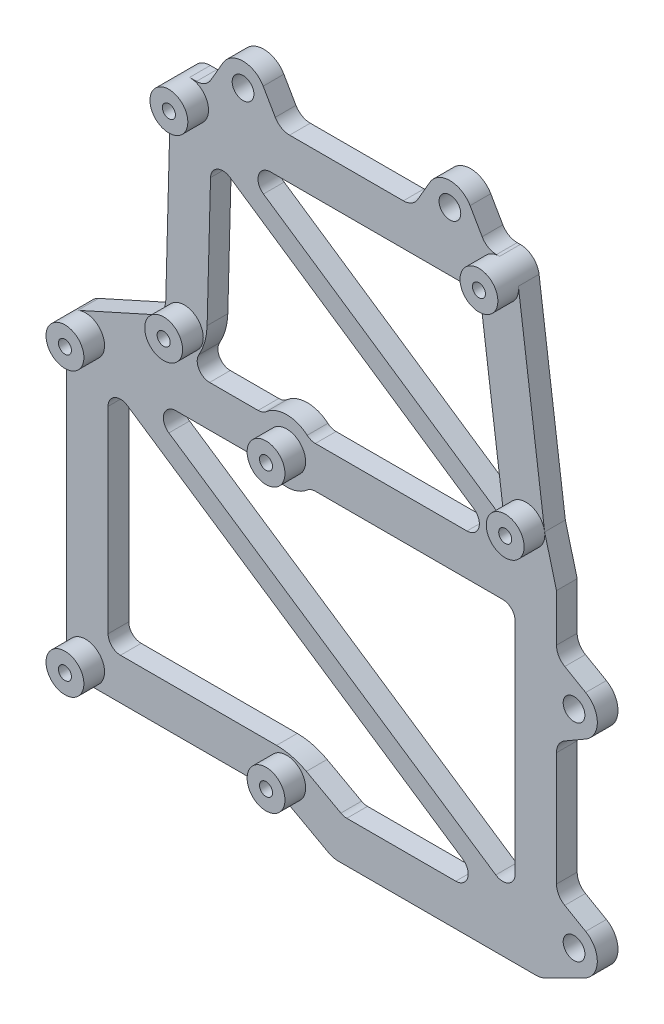
SolidWorks part; units mm, degrees
ref_plane "Front Plane" through (0, 0, 0) normal (0, 0, 1) x (1, 0, 0)
ref_plane "Top Plane" through (0, 0, 0) normal (0, 1, 0) x (1, 0, 0)
ref_plane "Right Plane" through (0, 0, 0) normal (1, 0, 0) x (0, 0, -1)
sketch "Sketch1" plane through (0, 0, 0) normal (0, 0, 1) x (1, 0, 0)
  line L0 (-89.9435, -52.835) -> (-7.3935, -52.835) construction
  line L1 (-88.6735, -4.575) -> (-13.7435, -4.575) construction
  line L2 (-89.9435, -52.835) -> (-13.7435, -4.575) construction
  line L3 (-88.6735, -4.575) -> (-7.3935, -52.835) construction
  line L4 (-88.6735, -3) -> (-13.7435, -3) construction
  line L5 (0, 0) -> (-100, 0) construction
  line L6 (0, 0) -> (0, -55.0748) construction
  line L7 (0, -55.0748) -> (-100, -55.0748) construction
  line L8 (-100, 0) -> (-100, -55.0748) construction
  line L9 (0, 0) -> (-100, -55.0748) construction
  line L10 (0, -55.0748) -> (-100, 0) construction
  line L11 (-113.8, -66.4248) -> (-65.2, -66.4248) construction
  line L12 (-62, -138.0748) -> (-117, -138.0748) construction
  line L13 (-62, -138.0748) -> (-62, -63.0748) construction
  line L14 (-62, -63.0748) -> (-117, -63.0748) construction
  line L15 (-117, -138.0748) -> (-117, -63.0748) construction
  line L16 (-62, -138.0748) -> (-117, -63.0748) construction
  line L17 (-62, -63.0748) -> (-117, -138.0748) construction
  line L18 (-65.2, -66.4248) -> (-65.2, -134.7248) construction
  line L19 (-65.2, -134.7248) -> (-113.8, -134.7248) construction
  line L20 (-65.2, -100.5748) -> (-89.5, -100.5748) construction
  line L21 (-89.5, -100.5748) -> (-89.5, -66.4248) construction
  line L22 (-94.517, -52.7145) -> (-93.2485, -4.575)
  line L23 (0, -146.0748) -> (-54, -146.0748)
  line L24 (0, -146.0748) -> (0, -63.0748)
  line L25 (0, -63.0748) -> (-54, -63.0748) construction
  line L26 (-54, -146.0748) -> (-54, -63.0748) construction
  line L27 (0, -146.0748) -> (-54, -63.0748) construction
  line L28 (0, -63.0748) -> (-54, -146.0748) construction
  line L29 (-88.6735, 0) -> (-13.7435, 0)
  line L30 (-9.2076, -3.9782) -> (-2.8576, -52.2382)
  line L31 (-2.8576, -52.2382) -> (0, -63.0748)
  line L32 (-54, -146.0748) -> (-66.3707, -139.2998)
  line L33 (-66.3707, -139.2998) -> (-113.8, -139.2998)
  line L34 (-118.375, -134.7248) -> (-118.375, -66.4248)
  line L35 (-115.6801, -62.254) -> (-94.517, -52.7145)
  circle A0 centre (-88.6735, -4.575) radius 1.575 construction
  circle A1 centre (-13.7435, -4.575) radius 1.575 construction
  circle A2 centre (-89.9435, -52.835) radius 1.575 construction
  circle A3 centre (-7.3935, -52.835) radius 1.575 construction
  circle A4 centre (-113.8, -66.4248) radius 1.575 construction
  circle A5 centre (-65.2, -66.4248) radius 1.575 construction
  circle A6 centre (-113.8, -134.7248) radius 1.575 construction
  circle A7 centre (-65.2, -134.7248) radius 1.575 construction
  circle A8 centre (-89.9435, -52.835) radius 4.575 construction
  circle A9 centre (-88.6735, -4.575) radius 4.575 construction
  circle A10 centre (-13.7435, -4.575) radius 4.575 construction
  circle A11 centre (-7.3935, -52.835) radius 4.575 construction
  circle A12 centre (-113.8, -66.4248) radius 4.575 construction
  circle A13 centre (-65.2, -66.4248) radius 4.575 construction
  circle A14 centre (-113.8, -134.7248) radius 4.575 construction
  circle A15 centre (-65.2, -134.7248) radius 4.575 construction
  arc A16 (-88.6735, 0) -> (-93.2485, -4.575) centre (-88.6735, -4.575) ccw
  arc A17 (-9.2076, -3.9782) -> (-13.7435, 0) centre (-13.7435, -4.575) ccw
  arc A18 (-118.375, -134.7248) -> (-113.8, -139.2998) centre (-113.8, -134.7248) ccw
  arc A19 (-118.375, -66.4248) -> (-115.6801, -62.254) centre (-113.8, -66.4248) cw
  point P8 (-50, -27.5374)
  point P17 (-89.5, -100.5748)
  point P31 (-27, -104.5748)
  dimension "D1" = 3.15
  dimension "D10" = 68.3
  dimension "D17" = 3
  dimension "D18" = 4.575
  dimension "D19" = 4.575
  dimension "D20" = 4.575
  dimension "D21" = 4.575
  dimension "D2" = 74.93
  dimension "D3" = 48.26
  dimension "D4" = 1.27
  dimension "D5" = 82.55
  dimension "D6" = 3
  dimension "D7" = 100
  dimension "D8" = 75
  dimension "D9" = 55
  dimension "D11" = 48.6
  dimension "D12" = 8
  dimension "D13" = 83
  dimension "D14" = 54
  dimension "D15" = 8
  dimension "D16" = 8
extrude "Boss-Extrude1" add sketch "Sketch1" along normal blind 5
fillet "Fillet1" radius 5 4 edges at (0, -146.0748, 2.5) (-54, -146.0748, 2.5) (-66.3707, -139.2998, 2.5) (-94.517, -52.7145, 2.5)
sketch "Sketch2" plane through (0, 0, 5) normal (0, 0, 1) x (1, 0, 0)
  circle A0 centre (-113.8, -66.4248) radius 1.575 construction
  circle A1 centre (-113.8, -66.4248) radius 1.575
  circle A2 centre (-7.3935, -52.835) radius 1.575 construction
  circle A3 centre (-13.7435, -4.575) radius 1.575 construction
  circle A4 centre (-13.7435, -4.575) radius 4.575 construction
  circle A5 centre (-7.3935, -52.835) radius 4.575 construction
  circle A6 centre (-89.9435, -52.835) radius 4.575 construction
  circle A7 centre (-89.9435, -52.835) radius 1.575 construction
  circle A8 centre (-88.6735, -4.575) radius 1.575 construction
  circle A9 centre (-88.6735, -4.575) radius 4.575 construction
  circle A10 centre (-65.2, -134.7248) radius 1.575 construction
  circle A11 centre (-65.2, -134.7248) radius 4.575 construction
  circle A12 centre (-65.2, -66.4248) radius 1.575 construction
  circle A13 centre (-65.2, -66.4248) radius 4.575 construction
  circle A14 centre (-113.8, -66.4248) radius 4.575 construction
  circle A15 centre (-113.8, -134.7248) radius 4.575 construction
  circle A16 centre (-113.8, -134.7248) radius 1.575 construction
  circle A17 centre (-7.3935, -52.835) radius 1.575
  circle A18 centre (-13.7435, -4.575) radius 1.575
  circle A19 centre (-13.7435, -4.575) radius 4.575
  circle A20 centre (-7.3935, -52.835) radius 4.575
  circle A21 centre (-89.9435, -52.835) radius 4.575
  circle A22 centre (-89.9435, -52.835) radius 1.575
  circle A23 centre (-88.6735, -4.575) radius 1.575
  circle A24 centre (-88.6735, -4.575) radius 4.575
  circle A25 centre (-65.2, -134.7248) radius 1.575
  circle A26 centre (-65.2, -134.7248) radius 4.575
  circle A27 centre (-65.2, -66.4248) radius 1.575
  circle A28 centre (-65.2, -66.4248) radius 4.575
  circle A29 centre (-113.8, -66.4248) radius 4.575
  circle A30 centre (-113.8, -134.7248) radius 4.575
  circle A31 centre (-113.8, -134.7248) radius 1.575
extrude "Boss-Extrude2" add sketch "Sketch2" along normal blind 5
sketch "Sketch3" plane through (0, 0, 5) normal (0, 0, 1) x (1, 0, 0)
  line L0 (-65.2, -61.4248) -> (-100.6345, -61.4248) construction
  line L1 (-65.2, -61.4248) -> (-10, -61.4248) construction
  line L2 (-93.2685, -63.1207) -> (-108.375, -69.9301) construction
  line L3 (-108.375, -69.9301) -> (-108.375, -129.2998) construction
  line L4 (-65.2, -66.4248) -> (-100.6345, -66.4248) construction
  line L5 (-10, -64.3712) -> (-12.6892, -54.1732) construction
  line L6 (-10, -136.0748) -> (-10, -64.3712) construction
  line L7 (-65.2, -66.4248) -> (-10, -66.4248) construction
  line L8 (0, -141.0748) -> (0, -63.0748) construction
  line L9 (-65.2, -71.4248) -> (-10, -71.4248) construction
  line L10 (-113.8, -66.4248) -> (-10, -136.0748) construction
  line L11 (-83.388, -10) -> (0, -66.4248) construction
  line L12 (-108.375, -73.0757) -> (-14.4868, -136.0748)
  line L13 (-101.8617, -71.4248) -> (-10, -133.0642)
  line L14 (-83.4662, -12.9657) -> (-11.8503, -61.4248)
  line L15 (-78.927, -10) -> (-12.4816, -54.9606)
  line L16 (-112.407, -64.3489) -> (-8.607, -133.9989) construction
  line L17 (-115.193, -68.5008) -> (-11.393, -138.1508) construction
  line L18 (-51.441, -136.0748) -> (-10, -136.0748) construction
  line L19 (-81.987, -7.9295) -> (1.401, -64.3543) construction
  line L20 (-18.5015, -10) -> (-83.388, -10) construction
  line L21 (-84.7891, -12.0705) -> (-1.401, -68.4954) construction
  line L22 (-83.388, -10) -> (-84.4378, -49.8409) construction
  line L30 (-10, -133.0642) -> (-10, -71.4248)
  line L31 (-12.4816, -54.9606) -> (-12.6892, -54.1732)
  line L32 (-12.6892, -54.1732) -> (-18.5015, -10)
  line L33 (-18.5015, -10) -> (-78.927, -10)
  line L34 (-83.4662, -12.9657) -> (-84.4378, -49.8409)
  line L36 (-108.375, -73.0757) -> (-108.375, -129.2998)
  line L37 (-108.375, -129.2998) -> (-67.6502, -129.2998)
  line L38 (-60.4451, -131.1436) -> (-51.441, -136.0748)
  line L39 (-51.441, -136.0748) -> (-14.4868, -136.0748)
  line L40 (0, -141.0748) -> (0, -63.0748)
  line L41 (-52.7205, -146.0748) -> (-5, -146.0748)
  line L42 (-65.2485, -139.9144) -> (-55.1222, -145.4602)
  line L43 (-113.8, -139.2998) -> (-67.6502, -139.2998)
  line L44 (-118.375, -66.4248) -> (-118.375, -134.7248)
  line L45 (-97.3779, -54.0041) -> (-115.6801, -62.254)
  line L46 (-93.2485, -4.575) -> (-94.4343, -49.5775)
  line L47 (-13.7435, 0) -> (-88.6735, 0)
  line L48 (-2.8576, -52.2382) -> (-9.2076, -3.9782)
  line L49 (0, -63.0748) -> (-2.8576, -52.2382)
  line L50 (0, -141.0748) -> (0, -63.0748)
  line L51 (-52.7205, -146.0748) -> (-5, -146.0748)
  line L52 (-65.2485, -139.9144) -> (-55.1222, -145.4602)
  line L53 (-113.8, -139.2998) -> (-67.6502, -139.2998)
  line L54 (-118.375, -66.4248) -> (-118.375, -134.7248)
  line L55 (-97.3779, -54.0041) -> (-115.6801, -62.254)
  line L56 (-93.2485, -4.575) -> (-94.4343, -49.5775)
  line L57 (-13.7435, 0) -> (-88.6735, 0)
  line L58 (-2.8576, -52.2382) -> (-9.2076, -3.9782)
  line L59 (0, -63.0748) -> (-2.8576, -52.2382)
  line L60 (-65.2, -66.4248) -> (0, -66.4248) construction
  line L61 (-65.2, -66.4248) -> (-109.225, -66.4248) construction
  line L62 (-70.8904, -71.4248) -> (-101.8617, -71.4248)
  line L63 (-59.5096, -71.4248) -> (-10, -71.4248)
  line L64 (-70.8904, -61.4248) -> (-90.4047, -61.4248)
  line L65 (-59.5096, -61.4248) -> (-11.8503, -61.4248)
  line L66 (-65.2, -71.4248) -> (-100.6345, -71.4248) construction
  arc A0 (-93.2685, -63.1207) -> (-84.4378, -49.8409) centre (-99.4326, -49.4458) ccw construction
  circle A1 centre (-113.8, -66.4248) radius 4.575 construction
  arc A2 (-118.375, -66.4248) -> (-115.6801, -62.254) centre (-113.8, -66.4248) ccw construction
  arc A3 (-70.8904, -71.4248) -> (-59.5096, -71.4248) centre (-65.2, -66.4248) ccw
  arc A27 (-18.5015, -10) -> (-18.5015, -10) centre (-18.5015, -10) ccw
  arc A28 (-83.388, -10) -> (-83.388, -10) centre (-83.388, -10) ccw
  arc A29 (-90.4047, -61.4248) -> (-84.4378, -49.8409) centre (-99.4326, -49.4458) ccw
  arc A30 (-108.375, -69.9301) -> (-108.375, -69.9301) centre (-108.375, -69.9301) ccw
  arc A31 (-108.375, -129.2998) -> (-108.375, -129.2998) centre (-108.375, -129.2998) ccw
  arc A32 (-60.4451, -131.1436) -> (-67.6502, -129.2998) centre (-67.6502, -144.2998) ccw
  arc A33 (-51.441, -136.0748) -> (-51.441, -136.0748) centre (-51.441, -136.0748) ccw
  arc A34 (-10, -136.0748) -> (-10, -136.0748) centre (-10, -136.0748) ccw
  arc A35 (-5, -146.0748) -> (0, -141.0748) centre (-5, -141.0748) ccw
  arc A36 (-55.1222, -145.4602) -> (-52.7205, -146.0748) centre (-52.7205, -141.0748) ccw
  arc A37 (-65.2485, -139.9144) -> (-67.6502, -139.2998) centre (-67.6502, -144.2998) ccw
  arc A38 (-118.375, -134.7248) -> (-113.8, -139.2998) centre (-113.8, -134.7248) ccw
  arc A39 (-115.6801, -62.254) -> (-118.375, -66.4248) centre (-113.8, -66.4248) ccw
  arc A40 (-97.3779, -54.0041) -> (-94.4343, -49.5775) centre (-99.4326, -49.4458) ccw
  arc A41 (-88.6735, 0) -> (-93.2485, -4.575) centre (-88.6735, -4.575) ccw
  arc A42 (-9.2076, -3.9782) -> (-13.7435, 0) centre (-13.7435, -4.575) ccw
  arc A43 (-5, -146.0748) -> (0, -141.0748) centre (-5, -141.0748) ccw
  arc A44 (-55.1222, -145.4602) -> (-52.7205, -146.0748) centre (-52.7205, -141.0748) ccw
  arc A45 (-65.2485, -139.9144) -> (-67.6502, -139.2998) centre (-67.6502, -144.2998) ccw
  arc A46 (-118.375, -134.7248) -> (-113.8, -139.2998) centre (-113.8, -134.7248) ccw
  arc A47 (-115.6801, -62.254) -> (-118.375, -66.4248) centre (-113.8, -66.4248) ccw
  arc A48 (-97.3779, -54.0041) -> (-94.4343, -49.5775) centre (-99.4326, -49.4458) ccw
  arc A49 (-88.6735, 0) -> (-93.2485, -4.575) centre (-88.6735, -4.575) ccw
  arc A50 (-9.2076, -3.9782) -> (-13.7435, 0) centre (-13.7435, -4.575) ccw
  arc A51 (-59.5096, -61.4248) -> (-70.8904, -61.4248) centre (-65.2, -66.4248) ccw
  circle A52 centre (-65.2, -66.4248) radius 4.575 construction
  circle A53 centre (-65.2, -66.4248) radius 4.575
  dimension "D3" = 3
  dimension "D1" = 0
  dimension "D2" = 10
  dimension "D4" = 5
  dimension "D5" = 5
  dimension "D6" = 2.5
  dimension "D7" = 2.5
  dimension "D8" = 2.5
  dimension "D9" = 2.5
extrude "Cut-Extrude1" cut sketch "Sketch3" against normal up to surface (5 mm away) contours A51 L65 L14 L34 A29 L64 | L32 L33 L15 L31 | A3 L62 L13 L30 L63 | A32 L38 L39 L12 L36 L37 region at (-76.3107, -112.748, 5) region at (-40.4429, -92.1122, 5) region at (-60.2537, -45.2476, 5) region at (-36.6741, -24.9619, 5) up to face at (-61.7558, -82.681, 0)
sketch "Sketch4" plane through (0, 0, 0) normal (0, 0, 1) x (1, 0, 0)
  line L0 (-126.2586, 4.2426) -> (4.2426, 4.2426) construction
  line L1 (4.2426, 4.2426) -> (4.2426, -135.7574) construction
  line L2 (0, 0) -> (4.2426, 4.2426) construction
  line L3 (-75.7574, 4.2426) -> (-75.7574, 0) construction
  line L4 (-80.6288, 7.0551) -> (-84.702, 0)
  line L5 (-70.886, 7.0551) -> (-66.8127, 0)
  line L6 (-84.702, 0) -> (-66.8127, 0)
  line L7 (-25.7574, 4.2426) -> (-25.7574, 0) construction
  line L8 (-30.6288, 7.0551) -> (-34.702, 0)
  line L9 (-20.886, 7.0551) -> (-16.8127, 0)
  line L10 (-34.702, 0) -> (-16.8127, 0)
  line L11 (4.2426, -85.7574) -> (0, -85.7574) construction
  line L12 (7.0551, -80.886) -> (0, -76.8127)
  line L13 (0, -141.0748) -> (0, -63.0748)
  line L14 (-52.7205, -146.0748) -> (-5, -146.0748)
  line L15 (-65.2485, -139.9144) -> (-55.1222, -145.4602)
  line L16 (-113.8, -139.2998) -> (-67.6502, -139.2998)
  line L17 (-118.375, -66.4248) -> (-118.375, -134.7248)
  line L18 (-97.3779, -54.0041) -> (-115.6801, -62.254)
  line L19 (-93.2485, -4.575) -> (-94.4343, -49.5775)
  line L20 (-13.7435, 0) -> (-88.6735, 0)
  line L21 (-2.8576, -52.2382) -> (-9.2076, -3.9782)
  line L22 (0, -63.0748) -> (-2.8576, -52.2382)
  line L23 (0, -141.0748) -> (0, -126.8127)
  line L25 (-65.2485, -139.9144) -> (-55.1222, -145.4602) construction
  line L26 (-113.8, -139.2998) -> (-67.6502, -139.2998) construction
  line L27 (-118.375, -66.4248) -> (-118.375, -134.7248) construction
  line L28 (-97.3779, -54.0041) -> (-115.6801, -62.254) construction
  line L29 (-93.2485, -4.575) -> (-94.4343, -49.5775) construction
  line L30 (-13.7435, 0) -> (-88.6735, 0) construction
  line L31 (-2.8576, -52.2382) -> (-9.2076, -3.9782) construction
  line L32 (0, -63.0748) -> (-2.8576, -52.2382) construction
  line L33 (0, -76.8127) -> (0, -94.702)
  line L34 (0, -94.702) -> (7.0551, -90.6288)
  line L35 (0, -126.8127) -> (7.0551, -130.886)
  line L36 (-2.7649, -145.5475) -> (6.7571, -140.7891)
  line L37 (4.2426, -135.7574) -> (0, -135.7574) construction
  line L38 (0, -94.702) -> (0, -63.0748) construction
  circle A0 centre (-75.7574, 4.2426) radius 2.625
  circle A1 centre (-25.7574, 4.2426) radius 2.625
  circle A2 centre (4.2426, -85.7574) radius 2.625
  circle A3 centre (4.2426, -135.7574) radius 2.625
  circle A4 centre (-75.7574, 4.2426) radius 5.625 construction
  circle A5 centre (-25.7574, 4.2426) radius 5.625 construction
  circle A6 centre (4.2426, -85.7574) radius 5.625 construction
  circle A7 centre (4.2426, -135.7574) radius 5.625 construction
  arc A8 (-80.6288, 7.0551) -> (-70.886, 7.0551) centre (-75.7574, 4.2426) cw
  arc A9 (-30.6288, 7.0551) -> (-20.886, 7.0551) centre (-25.7574, 4.2426) cw
  arc A10 (7.0551, -80.886) -> (7.0551, -90.6288) centre (4.2426, -85.7574) cw
  arc A11 (7.0551, -130.886) -> (6.7571, -140.7891) centre (4.2426, -135.7574) cw
  arc A16 (-5, -146.0748) -> (0, -141.0748) centre (-5, -141.0748) ccw
  arc A17 (-55.1222, -145.4602) -> (-52.7205, -146.0748) centre (-52.7205, -141.0748) ccw
  arc A18 (-65.2485, -139.9144) -> (-67.6502, -139.2998) centre (-67.6502, -144.2998) ccw
  arc A19 (-118.375, -134.7248) -> (-113.8, -139.2998) centre (-113.8, -134.7248) ccw
  arc A20 (-115.6801, -62.254) -> (-118.375, -66.4248) centre (-113.8, -66.4248) ccw
  arc A21 (-97.3779, -54.0041) -> (-94.4343, -49.5775) centre (-99.4326, -49.4458) ccw
  arc A22 (-88.6735, 0) -> (-93.2485, -4.575) centre (-88.6735, -4.575) ccw
  arc A23 (-9.2076, -3.9782) -> (-13.7435, 0) centre (-13.7435, -4.575) ccw
  arc A24 (-2.7649, -145.5475) -> (0, -141.0748) centre (-5, -141.0748) ccw
  arc A25 (-55.1222, -145.4602) -> (-52.7205, -146.0748) centre (-52.7205, -141.0748) ccw construction
  arc A26 (-65.2485, -139.9144) -> (-67.6502, -139.2998) centre (-67.6502, -144.2998) ccw construction
  arc A27 (-118.375, -134.7248) -> (-113.8, -139.2998) centre (-113.8, -134.7248) ccw construction
  arc A28 (-115.6801, -62.254) -> (-118.375, -66.4248) centre (-113.8, -66.4248) ccw construction
  arc A29 (-97.3779, -54.0041) -> (-94.4343, -49.5775) centre (-99.4326, -49.4458) ccw construction
  arc A30 (-88.6735, 0) -> (-93.2485, -4.575) centre (-88.6735, -4.575) ccw construction
  arc A31 (-9.2076, -3.9782) -> (-13.7435, 0) centre (-13.7435, -4.575) ccw construction
  dimension "D3" = 5.25
  dimension "D6" = 3
  dimension "D10" = 5.625
  dimension "D12" = 5.625
  dimension "D15" = 5.625
  dimension "D16" = 5.625
  dimension "D1" = 45
  dimension "D2" = 6
  dimension "D4" = 50
  dimension "D5" = 50
  dimension "D7" = 30
  dimension "D8" = 90
  dimension "D11" = 30
  dimension "D13" = 30
  dimension "D14" = 30
  dimension "D17" = 30
  dimension "D9" = 0
extrude "Boss-Extrude3" add sketch "Sketch4" along normal blind 5
fillet "Fillet2" [suppressed] radius 2
fillet "Fillet3" radius 3 17 edges at (-70.8904, -71.4248, 2.5) (-70.8904, -61.4248, 2.5) (-59.5096, -61.4248, 2.5) (-59.5096, -71.4248, 2.5) (-10, -71.4248, 2.5) (-10, -133.0642, 2.5) (-14.4868, -136.0748, 2.5) (-51.441, -136.0748, 2.5) (-108.375, -129.2998, 2.5) (-108.375, -73.0757, 2.5) (-101.8617, -71.4248, 2.5) (-18.5015, -10, 2.5) (-12.4816, -54.9606, 2.5) (-11.8503, -61.4248, 2.5) (-90.4047, -61.4248, 2.5) (-78.927, -10, 2.5) (-83.4662, -12.9657, 2.5)
fillet "Fillet4" radius 4 7 edges at (0, -126.8127, 2.5) (0, -94.702, 2.5) (0, -76.8127, 2.5) (-16.8127, 0, 2.5) (-34.702, 0, 2.5) (-66.8127, 0, 2.5) (-84.702, 0, 2.5)
